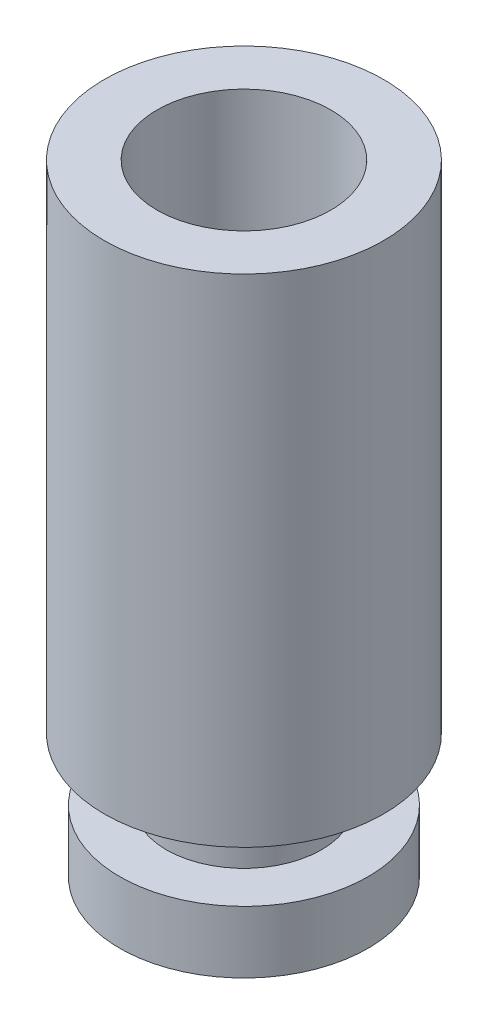
SolidWorks part; units mm, degrees
ref_plane "Front Plane" through (0, 0, 0) normal (0, 0, 1) x (1, 0, 0)
ref_plane "Top Plane" through (0, 0, 0) normal (0, 1, 0) x (1, 0, 0)
ref_plane "Right Plane" through (0, 0, 0) normal (1, 0, 0) x (0, 0, -1)
sketch "Sketch1" plane through (0, 0, 0) normal (0, 1, 0) x (1, 0, 0)
  circle A0 centre (-0.522, 0.5111) radius 1.375
  circle A1 centre (-0.522, 0.5111) radius 2.25
  dimension "D1" = 2.75
  dimension "D2" = 4.5
extrude "Boss-Extrude1" add sketch "Sketch1" along normal blind 8 contours A1
extrude "Boss-Extrude2" add sketch "Sketch1<3>" along normal blind 1 contours A0 region at (-0.522, 0, -0.5111)
sketch "Sketch1<3>" plane through (0, 0, 0) normal (0, 1, 0) x (1, 0, 0) same geometry as "Sketch1"
sketch "Sketch5" plane through (0, 0, 0) normal (0, -1, 0) x (1, 0, 0)
  circle A3 centre (-0.522, -0.5111) radius 1.25
  dimension "D1" = 2.5
extrude "Boss-Extrude3" add sketch "Sketch5" along normal blind 1 contours A3
sketch "Sketch6" plane through (0, -1, 0) normal (0, -1, 0) x (1, 0, 0)
  circle A0 centre (-0.522, -0.5111) radius 2
  dimension "D1" = 4
extrude "Boss-Extrude4" add sketch "Sketch6" along normal blind 1
sketch "Sketch8" plane through (0, -2, 0) normal (0, -1, 0) x (-1, 0, 0)
  circle A0 centre (0.522, 0.5111) radius 1.5
  dimension "D1" = 3
sketch "Sketch11" plane through (0, 8, 0) normal (0, 1, 0) x (1, 0, 0)
  text T0 "VIII" font "Century Gothic" height in points 5
sketch "Sketch12" plane through (0, 8, 0) normal (0, 1, 0) x (1, 0, 0)
  circle A0 centre (-0.522, 0.5111) radius 1.4
  dimension "D1" = 2.8
extrude "Cut-Extrude1" cut sketch "Sketch12" against normal blind 7.5
